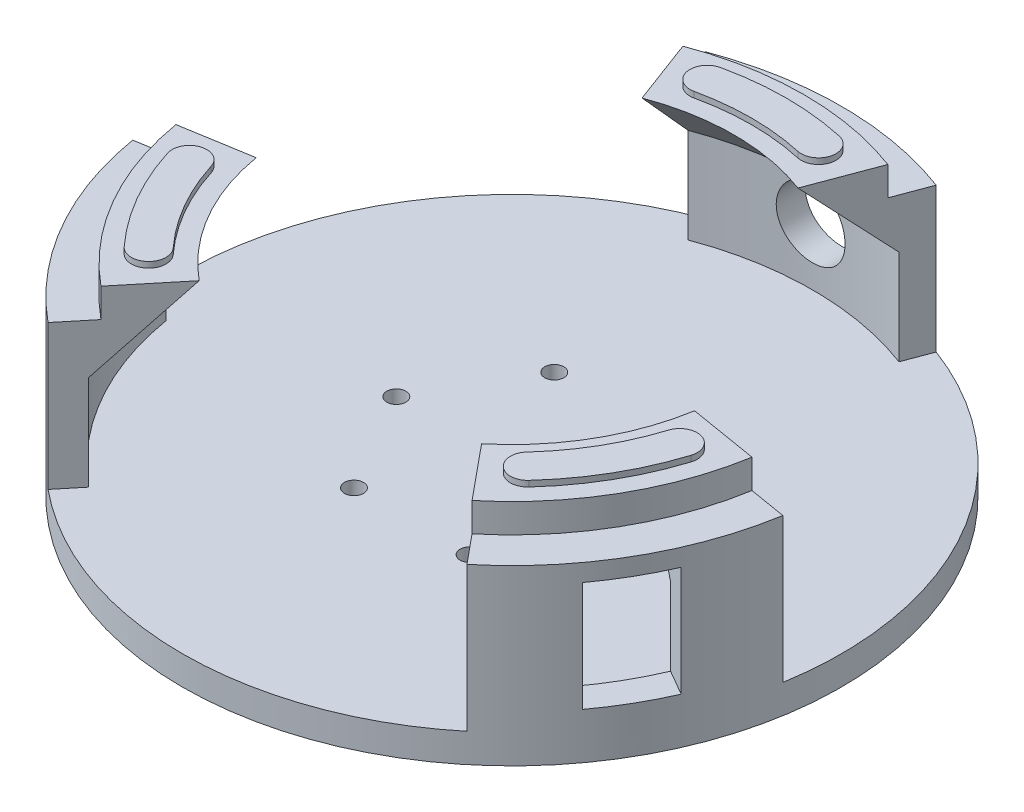
SolidWorks part; units mm, degrees
ref_plane "Front Plane" through (0, 0, 0) normal (0, 0, 1) x (1, 0, 0)
ref_plane "Top Plane" through (0, 0, 0) normal (0, 1, 0) x (1, 0, 0)
ref_plane "Right Plane" through (0, 0, 0) normal (1, 0, 0) x (0, 0, -1)
sketch "Sketch1" plane through (0, 0, 0) normal (0, 0, 1) x (1, 0, 0)
  line L1 (50.5, 20) -> (50.5, 15)
  line L2 (50.5, 15) -> (57, 15)
  line L3 (57, 15) -> (57, -15)
  line L4 (57, -15) -> (0, -15)
  line L7 (52, -10) -> (52, 6.4289)
  line L10 (0, 34.2778) -> (0, -25.6111) construction
  line L13 (38.4289, 20) -> (52, 6.4289)
  line L18 (0, -10) -> (52, -10)
  line L19 (38.4289, 20) -> (50.5, 20)
  line L20 (0, -15) -> (0, -10)
  point P12 (57, 0)
  dimension "D1" = 5
  dimension "D2" = 5
  dimension "D3" = 114
  dimension "D4" = 101
  dimension "D5" = 30
  dimension "D6" = 5
  dimension "D7" = 45
  dimension "D9" = 5
revolve "Revolve1" add sketch "Sketch1" angle 360 about L10
sketch "Sketch2" plane through (0, -10, 0) normal (0, 1, 0) x (1, 0, 0)
  line L2 (20, 53.376) -> (-20, 53.376) construction
  line L3 (56.225, -9.3675) -> (36.225, -44.0085) construction
  line L4 (0, 0) -> (36.225, -44.0085) construction
  line L5 (20, 53.376) -> (12.9825, 34.6476)
  line L6 (56.225, -9.3675) -> (36.4969, -6.0807)
  circle A0 centre (0, 0) radius 57 construction
  arc A1 (20, 53.376) -> (56.225, -9.3675) centre (0, 0) cw
  arc A2 (12.9825, 34.6476) -> (36.4969, -6.0807) centre (0, 0) cw
  dimension "D1" = 40
  dimension "D2" = 120
  dimension "D3" = 20
extrude "Cut-Extrude1" cut sketch "Sketch2" along normal through all
pattern_circular "CirPattern1" count 3 over 360 about axis through (0, 34.2778, 0) along (0, 1, 0) of "Cut-Extrude1"
sketch "Sketch3" plane through (0, 20, 0) normal (0, 1, 0) x (1, 0, 0)
  line L0 (-13.4838, 35.9857) -> (-17.7193, 47.2893) construction
  line L1 (-9.6239, 43.4105) -> (0, 0) construction
  line L2 (0, 0) -> (9.6239, 43.4105) construction
  arc A0 (-9.6239, 43.4105) -> (9.6239, 43.4105) centre (0, 0) cw construction
  arc A1 (10.2732, 46.3394) -> (-10.2732, 46.3394) centre (0, 0) ccw
  arc A2 (8.9746, 40.4816) -> (-8.9746, 40.4816) centre (0, 0) ccw
  arc A3 (8.9746, 40.4816) -> (10.2732, 46.3394) centre (9.6239, 43.4105) ccw
  arc A4 (-10.2732, 46.3394) -> (-8.9746, 40.4816) centre (-9.6239, 43.4105) ccw
  point P4 (0, 44.4645)
  point P16 (-15.6016, 41.6375)
  dimension "D1" = 3
  dimension "D2" = 25
  dimension "D3" = 44.4645
extrude "Boss-Extrude1" add sketch "Sketch3" along normal blind 1
pattern_circular "CirPattern2" count 3 over 360 about axis through (0, 34.2778, 0) along (0, 1, 0) of "Boss-Extrude1" reverse direction yes
sketch "Sketch4" plane through (0, -10, 0) normal (0, 1, 0) x (1, 0, 0)
  circle A0 centre (20, 0) radius 1.65
  dimension "D1" = 3.3
  dimension "D2" = 20
extrude "Cut-Extrude2" cut sketch "Sketch4" against normal through all
chamfer "Chamfer1" distance 2.5 angle 45 1 edges at (20, -15, 1.65)
pattern_circular "CirPattern3" count 6 over 360 about axis through (0, 34.2778, 0) along (0, 1, 0) of "Cut-Extrude2", "Chamfer1" reverse direction yes
sketch "Sketch5" plane through (0, 0, 0) normal (0, 0, 1) x (1, 0, 0)
  circle A0 centre (0, 0) radius 5.95
  dimension "D1" = 11.9
extrude "Cut-Extrude3" cut sketch "Sketch5" against normal through all
ref_plane "Plane1" through (-8.1125, 0, -4.6838) normal (-0.866, 0, -0.5) x (-0.5, 0, 0.866)
sketch "Sketch6" plane through (-8.1125, 0, -4.6838) normal (-0.866, 0, -0.5) x (-0.5, 0, 0.866)
  line L0 (0, 15) -> (0, -10) construction
  line L1 (-6.25, 12) -> (6.25, 12)
  line L2 (-6.25, 12) -> (-6.25, -7)
  line L3 (-6.25, -7) -> (6.25, -7)
  line L4 (6.25, 12) -> (6.25, -7)
  line L5 (20, 15) -> (-20, 15) construction
  line L6 (-20, -10) -> (-57, -10) construction
  point P4 (0, -7)
  point P10 (0, 0)
  point P13 (0, 2.5)
  point P14 (6.25, 2.5)
  dimension "D1" = 19
  dimension "D2" = 12.5
extrude "Cut-Extrude4" cut sketch "Sketch6" against normal through all
